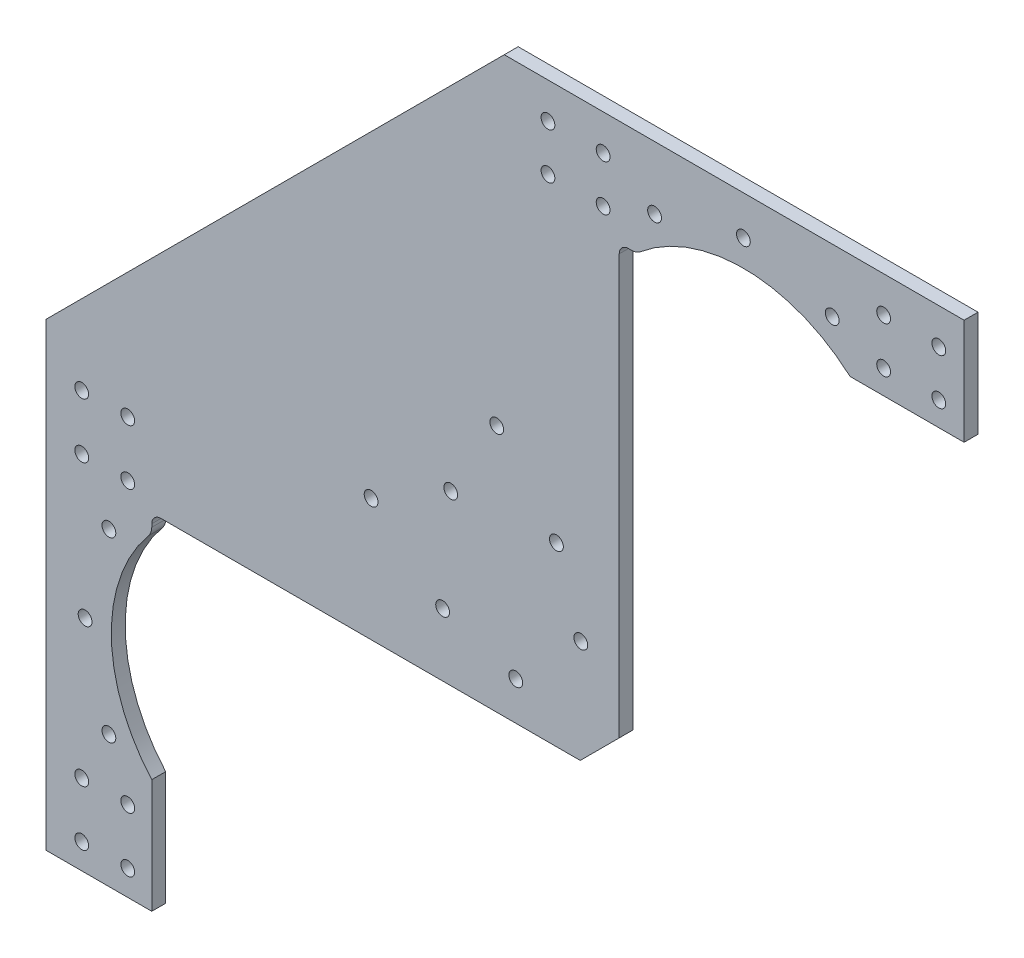
SolidWorks part; units mm, degrees
ref_plane "Front Plane" through (0, 0, 0) normal (0, 0, 1) x (1, 0, 0)
ref_plane "Top Plane" through (0, 0, 0) normal (0, 1, 0) x (1, 0, 0)
ref_plane "Right Plane" through (0, 0, 0) normal (1, 0, 0) x (0, 0, -1)
sketch "Sketch1" plane through (0, 0, 0) normal (0, 0, 1) x (1, 0, 0)
  line L0 (0, 0) -> (0, 128.66) construction
  line L1 (-151.66, -48) -> (-128.66, -48)
  line L2 (-151.66, -48) -> (-151.66, 52)
  line L4 (-128.66, -48) -> (-128.66, 27) construction
  line L5 (-52, 151.66) -> (48, 151.66)
  line L7 (-27, 128.66) -> (48, 128.66) construction
  line L8 (48, 151.66) -> (48, 128.66)
  line L9 (0, 0) -> (-128.66, 0) construction
  line L10 (-27, 128.66) -> (-128.66, 27) construction
  line L11 (-128.66, 128.66) -> (-27, 128.66) construction
  line L12 (-128.66, 27) -> (-128.66, 128.66) construction
  line L13 (-52, 151.66) -> (-151.66, 52)
  line L14 (-151.66, 151.66) -> (-52, 151.66) construction
  line L15 (-151.66, 52) -> (-151.66, 151.66) construction
  line L16 (-24.3179, 128.66) -> (-25, 128.66)
  line L17 (23.2069, 128.66) -> (48, 128.66)
  line L18 (-128.66, 25) -> (-128.66, 24.3179)
  line L19 (-128.66, -48) -> (-128.66, -23.2069)
  line L20 (-128.66, 23.2069) -> (-128.66, -23.2069) construction
  line L21 (-23.2069, 128.66) -> (23.2069, 128.66) construction
  line L22 (-126.66, 27) -> (-35.4853, 27)
  line L23 (-27, 35.4853) -> (-27, 126.66)
  line L24 (-35.4853, 27) -> (-27, 35.4853)
  line L25 (-25, 128.66) -> (-27, 128.66) construction
  line L26 (-27, 126.66) -> (-27, 128.66) construction
  line L27 (-128.66, 27) -> (-128.66, 25) construction
  line L28 (-128.66, 27) -> (-126.66, 27) construction
  line L29 (-23.2069, 128.66) -> (-24.3179, 128.66) construction
  line L30 (-128.66, 24.3179) -> (-128.66, 23.2069) construction
  arc A0 (23.2069, 128.66) -> (-22.3981, 129.3547) centre (0, 102.46) ccw
  arc A1 (-129.3547, 22.3981) -> (-128.66, -23.2069) centre (-102.46, 0) ccw
  arc A2 (-25, 128.66) -> (-27, 126.66) centre (-25, 126.66) ccw
  arc A3 (-126.66, 27) -> (-128.66, 25) centre (-126.66, 25) ccw
  arc A4 (-24.3179, 128.66) -> (-22.3981, 129.3547) centre (-24.3179, 131.66) ccw
  arc A5 (-22.3981, 129.3547) -> (-23.2069, 128.66) centre (0, 102.46) ccw construction
  arc A6 (-128.66, 24.3179) -> (-129.3547, 22.3981) centre (-131.66, 24.3179) cw
  arc A7 (-128.66, 23.2069) -> (-129.3547, 22.3981) centre (-102.46, 0) ccw construction
  dimension "D6" = 35
  dimension "D10" = 2
  dimension "D11" = 3
  dimension "D1" = 135
  dimension "D2" = 23
  dimension "D3" = 128.66
  dimension "D4" = 48
  dimension "D8" = 27
  dimension "D9" = 12
  dimension "D5" = 100
  dimension "D7" = 26.2
extrude "Boss-Extrude1" add sketch "Sketch1" along normal blind 3.0226
ref_axis "Axis1" through (0, 0, -0.1511) along (0, 0, 1)
sketch "Sketch3" plane through (0, 0, 3.0226) normal (0, 0, 1) x (1, 0, 0)
  line L1 (30.5, 143.8859) -> (30.5, 133.8859) construction
  line L2 (30.5, 143.8859) -> (42.5, 143.8859) construction
  line L3 (42.5, 143.8859) -> (42.5, 133.8859) construction
  line L4 (30.5, 133.8859) -> (42.5, 133.8859) construction
  line L16 (-30.5, 133.8859) -> (0, 133.8859) construction
  line L17 (0, 133.8859) -> (0, 0) construction
  line L18 (0, 133.8859) -> (30.5, 133.8859) construction
  line L19 (-133.8859, 0) -> (0, 0) construction
  line L20 (-133.8859, -30.5) -> (-133.8859, 0) construction
  line L21 (-133.8859, 0) -> (-133.8859, 30.5) construction
  line L30 (-42.5, 143.8859) -> (-42.5, 133.8859) construction
  line L31 (-42.5, 143.8859) -> (-30.5, 143.8859) construction
  line L32 (-30.5, 143.8859) -> (-30.5, 133.8859) construction
  line L33 (-42.5, 133.8859) -> (-30.5, 133.8859) construction
  line L34 (-143.8859, 42.5) -> (-143.8859, 30.5) construction
  line L35 (-143.8859, 42.5) -> (-133.8859, 42.5) construction
  line L36 (-133.8859, 42.5) -> (-133.8859, 30.5) construction
  line L37 (-143.8859, 30.5) -> (-133.8859, 30.5) construction
  line L38 (-143.8859, -30.5) -> (-143.8859, -42.5) construction
  line L39 (-143.8859, -30.5) -> (-133.8859, -30.5) construction
  line L40 (-133.8859, -30.5) -> (-133.8859, -42.5) construction
  line L41 (-143.8859, -42.5) -> (-133.8859, -42.5) construction
  circle A0 centre (30.5, 133.8859) radius 1.5
  circle A1 centre (30.5, 143.8859) radius 1.5
  circle A2 centre (42.5, 143.8859) radius 1.5
  circle A3 centre (42.5, 133.8859) radius 1.5
  circle A24 centre (-42.5, 133.8859) radius 1.5
  circle A25 centre (-42.5, 143.8859) radius 1.5
  circle A26 centre (-30.5, 143.8859) radius 1.5
  circle A27 centre (-30.5, 133.8859) radius 1.5
  circle A28 centre (-143.8859, 30.5) radius 1.5
  circle A29 centre (-143.8859, 42.5) radius 1.5
  circle A30 centre (-133.8859, 42.5) radius 1.5
  circle A31 centre (-133.8859, 30.5) radius 1.5
  circle A32 centre (-143.8859, -42.5) radius 1.5
  circle A33 centre (-143.8859, -30.5) radius 1.5
  circle A34 centre (-133.8859, -30.5) radius 1.5
  circle A35 centre (-133.8859, -42.5) radius 1.5
  dimension "D1" = 3
  dimension "D8" = 30.5
  dimension "D2" = 12
  dimension "D6" = 10
  dimension "D3" = 133.8859
extrude "Cut-Extrude1" cut sketch "Sketch3" against normal blind 10
sketch "Sketch4" plane through (0, 0, 3.0226) normal (0, 0, 1) x (1, 0, 0)
  line L0 (0, 0) -> (0, 143.16) construction
  line L1 (0, 0) -> (-63.6396, 63.6396) construction
  line L2 (0, 0) -> (-143.16, 0) construction
  line L3 (-137.9836, 19.3185) -> (-143.16, 0) construction
  line L4 (-143.16, 0) -> (-137.9836, -19.3185) construction
  line L5 (-80.9601, 53.6396) -> (-63.6396, 63.6396) construction
  line L6 (-63.6396, 63.6396) -> (-83.2677, 83.2677) construction
  line L7 (-19.3185, 137.9836) -> (0, 143.16) construction
  line L8 (-65.4074, 40.6586) -> (-40.6586, 65.4074) construction
  line L9 (-35.3553, 49.4975) -> (-49.4975, 35.3553) construction
  line L10 (-128.66, -48) -> (-128.66, -23.2069) construction
  line L11 (-35.4853, 27) -> (-27, 35.4853) construction
  circle A0 centre (-143.16, 0) radius 1.5
  circle A1 centre (-63.6396, 63.6396) radius 1.5
  circle A2 centre (0, 143.16) radius 1.5
  circle A3 centre (-80.9601, 53.6396) radius 1.5
  circle A4 centre (-53.6396, 80.9601) radius 1.5
  circle A5 centre (19.3185, 137.9836) radius 1.5
  circle A6 centre (-19.3185, 137.9836) radius 1.5
  circle A7 centre (-137.9836, 19.3185) radius 1.5
  circle A8 centre (-137.9836, -19.3185) radius 1.5
  circle A9 centre (-40.6586, 65.4074) radius 1.5
  circle A10 centre (-65.4074, 40.6586) radius 1.5
  circle A11 centre (-49.4975, 35.3553) radius 1.5
  circle A12 centre (-35.3553, 49.4975) radius 1.5
  dimension "D2" = 3
  dimension "D1" = 45
  dimension "D3" = 14.5
  dimension "D4" = 75
  dimension "D5" = 20
  dimension "D6" = 45.8162
  dimension "D7" = 75
  dimension "D8" = 75
  dimension "D9" = 35
  dimension "D10" = 20
  dimension "D11" = 15
  dimension "D12" = 15
extrude "Cut-Extrude2" cut sketch "Sketch4" against normal through all
ref_plane "Plane1" through (0, 0, 0) normal (-0.7071, -0.7071, 0) x (-0.7071, 0.7071, 0)
sketch "Sketch5" plane through (0, 0, 3.0226) normal (0, 0, 1) x (1, 0, 0)
  circle A0 centre (-76.6198, 82.5365) radius 9.6037
equation "\"EyeDiameter\" = 155"
equation "\"BasePlaneDistance\" = \"EyeDiameter\"/2+15"
equation "\"EyeClearance\" = 2"
equation "\"L2Thickness\" = 15"
equation "\"L2_ID\" = 20"
equation "\"Offset\"= - 2"
equation "\"D3@Sketch1\"=\"BasePlaneDistance\" + 38.16 +\"Offset\""
equation "\"D3@Sketch3\"=\"BasePlaneDistance\" - 37.34+78.72592343"
equation "\"D7@Sketch1\"=24.20 - \"Offset\""
equation "\"D2@Sketch1\"=25.00 + \"Offset\""
